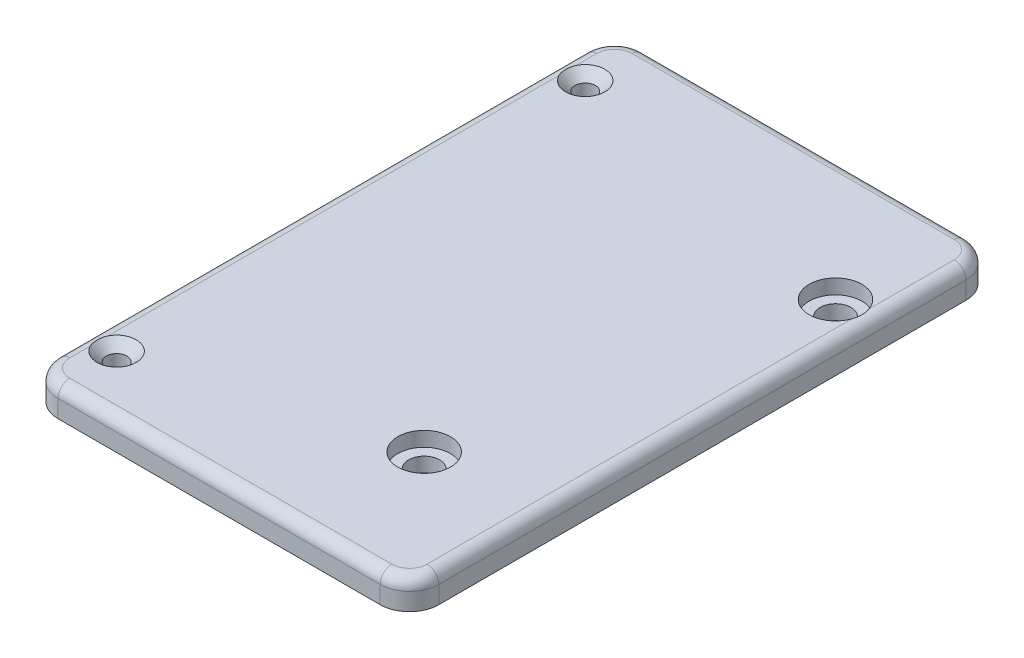
SolidWorks part; units mm, degrees
ref_plane "Front Plane" through (0, 0, 0) normal (0, 0, 1) x (1, 0, 0)
ref_plane "Top Plane" through (0, 0, 0) normal (0, 1, 0) x (1, 0, 0)
ref_plane "Right Plane" through (0, 0, 0) normal (1, 0, 0) x (0, 0, -1)
sketch "Sketch2" plane through (0, 0, 0) normal (0, 1, 0) x (1, 0, 0)
  line L1 (-32.5, 50) -> (32.5, 50)
  line L2 (-32.5, 50) -> (-32.5, -50)
  line L3 (-32.5, -50) -> (32.5, -50)
  line L4 (32.5, 50) -> (32.5, -50)
  line L5 (-32.5, 50) -> (32.5, -50) construction
  line L6 (-32.5, -50) -> (32.5, 50) construction
  circle A0 centre (-27.5, 40) radius 1.75
  circle A1 centre (-27.5, -40) radius 1.75
  circle A2 centre (26.23, 29) radius 2.65
  circle A3 centre (13.65, -28.65) radius 2.65
  point P0 (0, 0)
  dimension "D3" = 3.5
  dimension "D4" = 5
  dimension "D8" = 5.3
  dimension "D9" = 5.3
  dimension "D1" = 65
  dimension "D2" = 100
  dimension "D5" = 5
  dimension "D6" = 10
  dimension "D7" = 10
  dimension "D10" = 18.85
  dimension "D11" = 21.35
  dimension "D12" = 6.27
  dimension "D13" = 21
extrude "Boss-Extrude1" add sketch "Sketch2" along normal blind 5
sketch "Sketch3" plane through (0, 5, 0) normal (0, 1, 0) x (1, 0, 0)
  circle A0 centre (26.23, 29) radius 4.5
  circle A1 centre (13.65, -28.65) radius 4.5
  dimension "D1" = 9
  dimension "D2" = 9
extrude "Cut-Extrude1" cut sketch "Sketch3" against normal blind 2.5
fillet "Fillet1" radius 5 4 edges at (32.5, 2.5, 50) (-32.5, 2.5, -50) (32.5, 2.5, -50) (-32.5, 2.5, 50)
chamfer "Chamfer1" distance 1.6 angle 45 2 edges at (-27.5, 5, 41.75) (-27.5, 5, -38.25)
fillet "Fillet2" radius 2 8 edges at (-31.0355, 5, 48.5355) (-32.5, 5, 0) (-31.0355, 5, -48.5355) (0, 5, -50) (31.0355, 5, -48.5355) (32.5, 5, 0) (31.0355, 5, 48.5355) (0, 5, 50)
